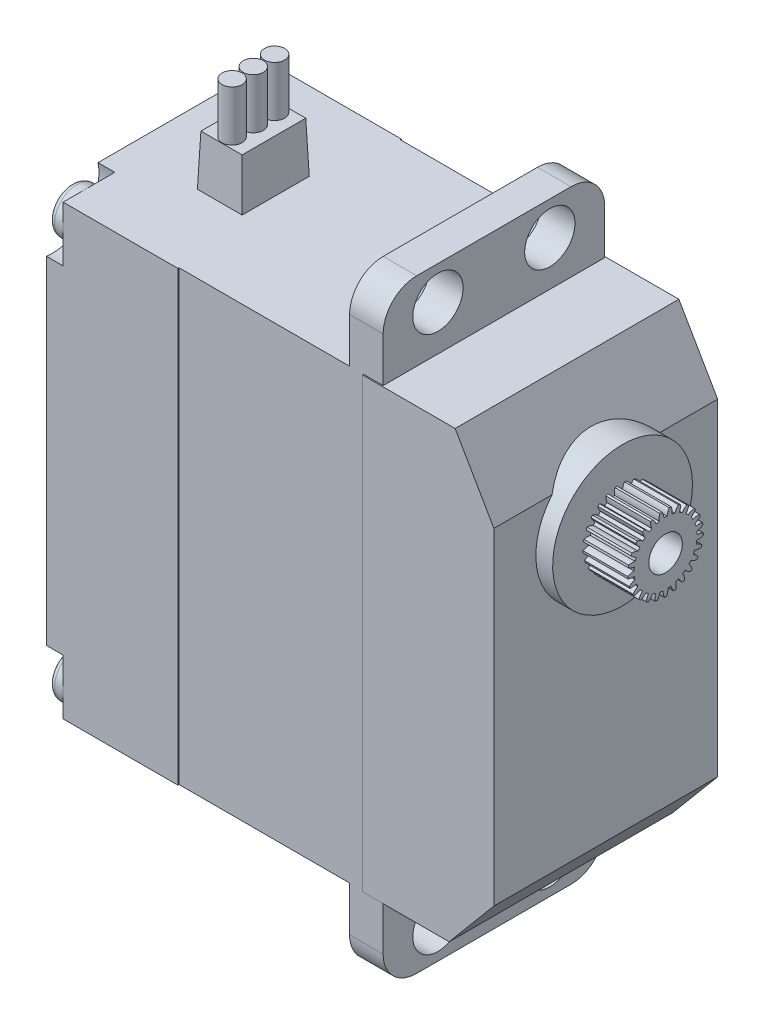
SolidWorks part; units mm, degrees
ref_plane "前视基准面" through (0, 0, 0) normal (0, 0, 1) x (1, 0, 0)
ref_plane "上视基准面" through (0, 0, 0) normal (0, 1, 0) x (1, 0, 0)
ref_plane "右视基准面" through (0, 0, 0) normal (1, 0, 0) x (0, 0, -1)
sketch "草图1" plane through (0, 0, 0) normal (0, 0, 1) x (1, 0, 0)
  line L1 (-20, -20) -> (20, -20)
  line L2 (-20, -20) -> (-20, 20)
  line L3 (-20, 20) -> (20, 20)
  line L4 (20, -20) -> (20, 20)
  line L5 (-20, -20) -> (20, 20) construction
  line L6 (-20, 20) -> (20, -20) construction
  point P0 (0, 0)
  dimension "D1" = 40
  dimension "D2" = 40
extrude "凸台-拉伸1" add sketch "草图1" along normal blind 20
ref_plane "基准面1" through (20, 0, 0) normal (1, 0, 0) x (0, 0, -1)
sketch "草图2" plane through (20, 0, 0) normal (1, 0, 0) x (0, 0, -1)
  line L0 (-10, 20) -> (-10, 10) construction
  line L1 (-20, 20) -> (0, 20) construction
  circle A0 centre (-10, 10) radius 6.25
  dimension "D2" = 12.5
  dimension "D1" = 10
extrude "凸台-拉伸2" add sketch "草图2" along normal blind 1.5
ref_plane "基准面2" through (-20, 0, 0) normal (-1, 0, 0) x (0, 0, 1)
ref_plane "基准面5" through (20, 0, 0) normal (1, 0, 0) x (0, 0, -1)
ref_plane "基准面8" through (0, 0, 0) normal (0, 0, -1) x (-1, 0, 0)
sketch "草图10" plane through (0, 0, 0) normal (0, 0, -1) x (-1, 0, 0)
  line L0 (-20, 20) -> (20, 20) construction
  line L1 (-8.25, -20) -> (8.25, -20)
  line L2 (-8.25, -20) -> (-8.25, 20)
  line L3 (-8.25, 20) -> (8.25, 20)
  line L4 (8.25, -20) -> (8.25, 20)
  line L5 (-8.25, -20) -> (8.25, 20) construction
  line L6 (-8.25, 20) -> (8.25, -20) construction
  point P0 (0, 0)
  dimension "D1" = 16.5
extrude "切除-拉伸5" cut sketch "草图10" against normal blind 0.1
ref_plane "基准面9" through (0, 0, 20) normal (0, 0, 1) x (1, 0, 0)
sketch "草图11" plane through (0, 0, 20) normal (0, 0, 1) x (1, 0, 0)
  line L0 (20, 20) -> (-20, 20) construction
  line L1 (-8.25, -20) -> (8.25, -20)
  line L2 (-8.25, -20) -> (-8.25, 20)
  line L3 (-8.25, 20) -> (8.25, 20)
  line L4 (8.25, -20) -> (8.25, 20)
  line L5 (-8.25, -20) -> (8.25, 20) construction
  line L6 (-8.25, 20) -> (8.25, -20) construction
  point P0 (0, 0)
  dimension "D1" = 16.5
extrude "切除-拉伸6" cut sketch "草图11" against normal blind 0.1
ref_plane "基准面10" through (0, 20, 0) normal (0, 1, 0) x (1, 0, 0)
ref_plane "基准面11" through (0, -20, 0) normal (0, -1, 0) x (-1, 0, 0)
ref_plane "基准面12" through (21.5, 0, 0) normal (1, 0, 0) x (0, 0, -1)
sketch "草图14" plane through (21.5, 0, 0) normal (1, 0, 0) x (0, 0, -1)
  arc A0 (-9.0018, 13.0728) -> (-9.3214, 12.5861) centre (-8.1454, 12.1623) ccw
  arc A1 (-9.3214, 12.5861) -> (-9.5931, 12.6558) centre (-10.1556, 9.9012) ccw
  arc A2 (-9.5931, 12.6558) -> (-9.6387, 13.2363) centre (-10.8278, 12.851) ccw
  arc A3 (-9.6387, 13.2363) -> (-9.8268, 13.2601) centre (-10.1556, 9.9012) ccw
  arc A4 (-9.8268, 13.2601) -> (-10.0153, 12.7092) centre (-8.7709, 12.5912) ccw
  arc A5 (-10.0153, 12.7092) -> (-10.2958, 12.7092) centre (-10.1556, 9.9012) ccw
  arc A6 (-10.2958, 12.7092) -> (-10.4843, 13.2601) centre (-11.5402, 12.5912) ccw
  arc A7 (-10.4843, 13.2601) -> (-10.6725, 13.2363) centre (-10.1556, 9.9012) ccw
  arc A8 (-10.6725, 13.2363) -> (-10.718, 12.6558) centre (-9.4834, 12.851) ccw
  arc A9 (-10.718, 12.6558) -> (-10.9897, 12.5861) centre (-10.1556, 9.9012) ccw
  arc A10 (-10.9897, 12.5861) -> (-11.3093, 13.0728) centre (-12.1657, 12.1623) ccw
  arc A11 (-11.3093, 13.0728) -> (-11.4857, 13.003) centre (-10.1556, 9.9012) ccw
  arc A12 (-11.4857, 13.003) -> (-11.3854, 12.4294) centre (-10.2381, 12.9255) ccw
  arc A13 (-11.3854, 12.4294) -> (-11.6312, 12.2943) centre (-10.1556, 9.9012) ccw
  arc A14 (-11.6312, 12.2943) -> (-12.0618, 12.6863) centre (-12.6649, 11.5913) ccw
  arc A15 (-12.0618, 12.6863) -> (-12.2153, 12.5748) centre (-10.1556, 9.9012) ccw
  arc A16 (-12.2153, 12.5748) -> (-11.9755, 12.0441) centre (-10.9876, 12.81) ccw
  arc A17 (-11.9755, 12.0441) -> (-12.18, 11.8521) centre (-10.1556, 9.9012) ccw
  arc A18 (-12.18, 11.8521) -> (-12.6946, 12.1247) centre (-13.0064, 10.9142) ccw
  arc A19 (-12.6946, 12.1247) -> (-12.8155, 11.9785) centre (-10.1556, 9.9012) ccw
  arc A20 (-12.8155, 11.9785) -> (-12.4513, 11.5242) centre (-11.6848, 12.5117) ccw
  arc A21 (-12.4513, 11.5242) -> (-12.6016, 11.2873) centre (-10.1556, 9.9012) ccw
  arc A22 (-12.6016, 11.2873) -> (-13.1678, 11.4234) centre (-13.1688, 10.1734) ccw
  arc A23 (-13.1678, 11.4234) -> (-13.2485, 11.2518) centre (-10.1556, 9.9012) ccw
  arc A24 (-13.2485, 11.2518) -> (-12.7828, 10.9023) centre (-12.286, 12.0493) ccw
  arc A25 (-12.7828, 10.9023) -> (-12.8695, 10.6355) centre (-10.1556, 9.9012) ccw
  arc A26 (-12.8695, 10.6355) -> (-13.4517, 10.6265) centre (-13.1418, 9.4155) ccw
  arc A27 (-13.4517, 10.6265) -> (-13.4872, 10.4402) centre (-10.1556, 9.9012) ccw
  arc A28 (-13.4872, 10.4402) -> (-12.9492, 10.2175) centre (-12.7533, 11.452) ccw
  arc A29 (-12.9492, 10.2175) -> (-12.9668, 9.9375) centre (-10.1556, 9.9012) ccw
  arc A30 (-12.9668, 9.9375) -> (-13.5285, 9.784) centre (-12.9272, 8.6881) ccw
  arc A31 (-13.5285, 9.784) -> (-13.5166, 9.5947) centre (-10.1556, 9.9012) ccw
  arc A32 (-13.5166, 9.5947) -> (-12.9401, 9.5128) centre (-13.0574, 10.7573) ccw
  arc A33 (-12.9401, 9.5128) -> (-12.8875, 9.2372) centre (-10.1556, 9.9012) ccw
  arc A34 (-12.8875, 9.2372) -> (-13.3934, 8.9488) centre (-12.5384, 8.0369) ccw
  arc A35 (-13.3934, 8.9488) -> (-13.3348, 8.7685) centre (-10.1556, 9.9012) ccw
  arc A36 (-13.3348, 8.7685) -> (-12.756, 8.8325) centre (-13.1791, 10.0087) ccw
  arc A37 (-12.756, 8.8325) -> (-12.6366, 8.5787) centre (-10.1556, 9.9012) ccw
  arc A38 (-12.6366, 8.5787) -> (-13.0549, 8.1735) centre (-12, 7.5029) ccw
  arc A39 (-13.0549, 8.1735) -> (-12.9532, 8.0134) centre (-10.1556, 9.9012) ccw
  arc A40 (-12.9532, 8.0134) -> (-12.4086, 8.2194) centre (-13.1109, 9.2534) ccw
  arc A41 (-12.4086, 8.2194) -> (-12.2298, 8.0032) centre (-10.1556, 9.9012) ccw
  arc A42 (-12.2298, 8.0032) -> (-12.5341, 7.5068) centre (-11.3456, 7.1196) ccw
  arc A43 (-12.5341, 7.5068) -> (-12.3959, 7.3769) centre (-10.1556, 9.9012) ccw
  arc A44 (-12.3959, 7.3769) -> (-11.9195, 7.7119) centre (-12.8569, 8.5388) ccw
  arc A45 (-11.9195, 7.7119) -> (-11.6926, 7.547) centre (-10.1556, 9.9012) ccw
  arc A46 (-11.6926, 7.547) -> (-11.8639, 6.9905) centre (-10.6165, 6.911) ccw
  arc A47 (-11.8639, 6.9905) -> (-11.6977, 6.8991) centre (-10.1556, 9.9012) ccw
  arc A48 (-11.6977, 6.8991) -> (-11.3197, 7.342) centre (-12.4333, 7.9098) ccw
  arc A49 (-11.3197, 7.342) -> (-11.0588, 7.2387) centre (-10.1556, 9.9012) ccw
  arc A50 (-11.0588, 7.2387) -> (-11.0864, 6.6571) centre (-9.8584, 6.8903) ccw
  arc A51 (-11.0864, 6.6571) -> (-10.9027, 6.6099) centre (-10.1556, 9.9012) ccw
  arc A52 (-10.9027, 6.6099) -> (-10.6467, 7.1329) centre (-11.8665, 7.4059) ccw
  arc A53 (-10.6467, 7.1329) -> (-10.3683, 7.0977) centre (-10.1556, 9.9012) ccw
  arc A54 (-10.3683, 7.0977) -> (-10.2504, 6.5275) centre (-9.1189, 7.0588) ccw
  arc A55 (-10.2504, 6.5275) -> (-10.0607, 6.5275) centre (-10.1556, 9.9012) ccw
  arc A56 (-10.0607, 6.5275) -> (-9.9428, 7.0977) centre (-11.1922, 7.0588) ccw
  arc A57 (-9.9428, 7.0977) -> (-9.6645, 7.1329) centre (-10.1556, 9.9012) ccw
  arc A58 (-9.6645, 7.1329) -> (-9.4084, 6.6099) centre (-8.4447, 7.4059) ccw
  arc A59 (-9.4084, 6.6099) -> (-9.2247, 6.6571) centre (-10.1556, 9.9012) ccw
  arc A60 (-9.2247, 6.6571) -> (-9.2523, 7.2387) centre (-10.4528, 6.8903) ccw
  arc A61 (-9.2523, 7.2387) -> (-8.9915, 7.342) centre (-10.1556, 9.9012) ccw
  arc A62 (-8.9915, 7.342) -> (-8.6134, 6.8991) centre (-7.8779, 7.9098) ccw
  arc A63 (-8.6134, 6.8991) -> (-8.4472, 6.9905) centre (-10.1556, 9.9012) ccw
  arc A64 (-8.4472, 6.9905) -> (-8.6185, 7.547) centre (-9.6947, 6.911) ccw
  arc A65 (-8.6185, 7.547) -> (-8.3916, 7.7119) centre (-10.1556, 9.9012) ccw
  arc A66 (-8.3916, 7.7119) -> (-7.9153, 7.3769) centre (-7.4542, 8.5388) ccw
  arc A67 (-7.9153, 7.3769) -> (-7.777, 7.5068) centre (-10.1556, 9.9012) ccw
  arc A68 (-7.777, 7.5068) -> (-8.0814, 8.0032) centre (-8.9655, 7.1196) ccw
  arc A69 (-8.0814, 8.0032) -> (-7.9026, 8.2194) centre (-10.1556, 9.9012) ccw
  arc A70 (-7.9026, 8.2194) -> (-7.3579, 8.0134) centre (-7.2003, 9.2534) ccw
  arc A71 (-7.3579, 8.0134) -> (-7.2563, 8.1735) centre (-10.1556, 9.9012) ccw
  arc A72 (-7.2563, 8.1735) -> (-7.6745, 8.5787) centre (-8.3112, 7.5029) ccw
  arc A73 (-7.6745, 8.5787) -> (-7.5551, 8.8325) centre (-10.1556, 9.9012) ccw
  arc A74 (-7.5551, 8.8325) -> (-6.9763, 8.7685) centre (-7.132, 10.0087) ccw
  arc A75 (-6.9763, 8.7685) -> (-6.9177, 8.9488) centre (-10.1556, 9.9012) ccw
  arc A76 (-6.9177, 8.9488) -> (-7.4236, 9.2372) centre (-7.7727, 8.0369) ccw
  arc A77 (-7.4236, 9.2372) -> (-7.371, 9.5128) centre (-10.1556, 9.9012) ccw
  arc A78 (-7.371, 9.5128) -> (-6.7945, 9.5947) centre (-7.2538, 10.7573) ccw
  arc A79 (-6.7945, 9.5947) -> (-6.7826, 9.784) centre (-10.1556, 9.9012) ccw
  arc A80 (-6.7826, 9.784) -> (-7.3443, 9.9375) centre (-7.3839, 8.6881) ccw
  arc A81 (-7.3443, 9.9375) -> (-7.3619, 10.2175) centre (-10.1556, 9.9012) ccw
  arc A82 (-7.3619, 10.2175) -> (-6.8239, 10.4402) centre (-7.5578, 11.452) ccw
  arc A83 (-6.8239, 10.4402) -> (-6.8594, 10.6265) centre (-10.1556, 9.9012) ccw
  arc A84 (-6.8594, 10.6265) -> (-7.4417, 10.6355) centre (-7.1693, 9.4155) ccw
  arc A85 (-7.4417, 10.6355) -> (-7.5283, 10.9023) centre (-10.1556, 9.9012) ccw
  arc A86 (-7.5283, 10.9023) -> (-7.0626, 11.2518) centre (-8.0251, 12.0493) ccw
  arc A87 (-7.0626, 11.2518) -> (-7.1434, 11.4234) centre (-10.1556, 9.9012) ccw
  arc A88 (-7.1434, 11.4234) -> (-7.7095, 11.2873) centre (-7.1424, 10.1734) ccw
  arc A89 (-7.7095, 11.2873) -> (-7.8599, 11.5242) centre (-10.1556, 9.9012) ccw
  arc A90 (-7.8599, 11.5242) -> (-7.4957, 11.9785) centre (-8.6263, 12.5117) ccw
  arc A91 (-7.4957, 11.9785) -> (-7.6166, 12.1247) centre (-10.1556, 9.9012) ccw
  arc A92 (-7.6166, 12.1247) -> (-8.1311, 11.8521) centre (-7.3047, 10.9142) ccw
  arc A93 (-8.1311, 11.8521) -> (-8.3356, 12.0441) centre (-10.1556, 9.9012) ccw
  arc A94 (-8.3356, 12.0441) -> (-8.0959, 12.5748) centre (-9.3235, 12.81) ccw
  arc A95 (-8.0959, 12.5748) -> (-8.2493, 12.6863) centre (-10.1556, 9.9012) ccw
  arc A96 (-8.2493, 12.6863) -> (-8.6799, 12.2943) centre (-7.6462, 11.5913) ccw
  arc A97 (-8.6799, 12.2943) -> (-8.9257, 12.4294) centre (-10.1556, 9.9012) ccw
  arc A98 (-8.9257, 12.4294) -> (-8.8255, 13.003) centre (-10.0731, 12.9255) ccw
  arc A99 (-8.8255, 13.003) -> (-9.0018, 13.0728) centre (-10.1556, 9.9012) ccw
extrude "凸台-拉伸6" add sketch "草图14" along normal blind 4
ref_plane "基准面13" through (25.5, 0, 0) normal (1, 0, 0) x (0, 0, -1)
sketch "草图15" plane through (25.5, 0, 0) normal (1, 0, 0) x (0, 0, -1)
  circle A0 centre (-10.1556, 9.9012) radius 1.5
extrude "切除-拉伸9" cut sketch "草图15" against normal blind 4
ref_plane "基准面14" through (0, 20, 0) normal (0, 1, 0) x (1, 0, 0)
ref_plane "基准面15" through (-20, 0, 0) normal (-1, 0, 0) x (0, 0, 1)
chamfer "倒角2" distance 6 angle 30 1 edges at (20, 20, 10) first distance on face at (20, 0, 10)
chamfer "倒角3" distance 4 angle 50 1 edges at (20, -20, 10) first distance on face at (0, -20, 10)
ref_plane "基准面18" through (0, -20, 0) normal (0, -1, 0) x (-1, 0, 0)
sketch "草图20" plane through (0, -20, 0) normal (0, -1, 0) x (-1, 0, 0)
  line L0 (-20, 1.0461) -> (-20, -15.8444) construction
  line L2 (-20, 0) -> (-7, 0) construction
  line L3 (6.4625, 0) -> (-6.4625, 0) construction
  line L4 (-7, 0) -> (-7, -0.8546) construction
  line L7 (-5.9416, -19.9) -> (-4.5261, -19.9) construction
  line L9 (-6.0182, -0.1) -> (-4.3371, -0.1) construction
  line L10 (-7, -0.1) -> (-7, -19.9) construction
  line L11 (-7, -19.9) -> (-10, -19.9) construction
  line L12 (-10, -19.9) -> (-10, 0) construction
  line L13 (-10, 0) -> (-7, 0) construction
  line L14 (-10, -0.1) -> (-7, -0.1)
  line L15 (-7, -0.1) -> (-7, -19.9)
  line L16 (-7, -19.9) -> (-10, -19.9)
  line L17 (-10, -19.9) -> (-10, -0.1)
extrude "凸台-拉伸8" add sketch "草图20" along normal blind 7
sketch "草图21" plane through (0, 20, 0) normal (0, 1, 0) x (1, 0, 0)
  line L6 (7, -19.9) -> (10, -19.9)
  line L7 (7, -0.1) -> (7, -19.9)
  line L8 (10, -0.1) -> (7, -0.1)
  line L9 (10, -19.9) -> (10, -0.1)
  line L10 (7, -19.9) -> (10, -19.9)
  line L11 (7, -0.1) -> (7, -19.9)
  line L12 (10, -0.1) -> (7, -0.1)
  line L13 (10, -19.9) -> (10, -0.1)
  dimension "D1" = 0
extrude "凸台-拉伸9" add sketch "草图21" along normal blind 7
fillet "圆角4" radius 3 4 edges at (8.5, 27, 19.9) (8.5, 27, 0.1) (8.5, -27, 19.9) (8.5, -27, 0.1)
ref_plane "基准面19" through (10, 0, 0) normal (1, 0, 0) x (0, 0, -1)
sketch "草图22" plane through (10, 0, 0) normal (1, 0, 0) x (0, 0, -1)
  line L3 (-20.5235, 0) -> (-0.5503, 0) construction
  circle A0 centre (-15, 24) radius 2.25
  circle A1 centre (-5, 24) radius 2.25
  circle A2 centre (-5, -24) radius 2.25
  circle A3 centre (-15, -24) radius 2.25
extrude "切除-拉伸12" cut sketch "草图22" against normal blind 7.3
sketch "草图24" plane through (-20, 0, 0) normal (-1, 0, 0) x (0, 0, 1)
  line L0 (20, 0) -> (0, 0) construction
  line L1 (20, -6.4625) -> (20, 6.4625) construction
  line L2 (10, 0) -> (10, 28.881) construction
  line L3 (0, 6.4625) -> (0, -6.4625) construction
  line L4 (11, 20) -> (-11, 20) construction
  line L5 (0, 15.0598) -> (0, 20)
  line L6 (0, 20) -> (4.6197, 20)
  line L7 (20, 15.0598) -> (20, 20)
  line L8 (20, 20) -> (15.3803, 20)
  line L9 (0, -20) -> (4.6197, -20)
  line L10 (0, -15.0598) -> (0, -20)
  line L11 (20, -20) -> (15.3803, -20)
  line L12 (20, -15.0598) -> (20, -20)
  arc A1 (4.6197, 20) -> (0, 15.0598) centre (0.55, 19.1756) cw
  arc A2 (15.3803, 20) -> (20, 15.0598) centre (19.45, 19.1756) ccw
  arc A3 (4.6197, -20) -> (0, -15.0598) centre (0.55, -19.1756) ccw
  arc A5 (15.3803, -20) -> (20, -15.0598) centre (19.45, -19.1756) cw
extrude "切除-拉伸13" cut sketch "草图24" against normal blind 1.5
ref_plane "基准面20" through (-18.5, 0, 0) normal (-1, 0, 0) x (0, 0, 1)
sketch "草图25" plane through (-18.5, 0, 0) normal (-1, 0, 0) x (0, 0, 1)
  line L0 (0, 0) -> (20, 0) construction
  line L1 (20, -6.4625) -> (20, 6.4625) construction
  line L2 (10, 0) -> (10, 8.1993) construction
  circle A0 centre (2.0399, 17.9472) radius 2
  circle A1 centre (17.9601, 17.9472) radius 2
  circle A2 centre (2.0399, -17.9472) radius 2
  circle A3 centre (17.9601, -17.9472) radius 2
extrude "凸台-拉伸10" add sketch "草图25" along normal blind 1.3
fillet "圆角5" radius 0.5 4 edges at (-19.8, -17.9472, 19.9601) (-19.8, -17.9472, 0.0399) (-19.8, 17.9472, 15.9601) (-19.8, 17.9472, 4.0399)
ref_plane "基准面21" through (-19.8, 0, 0) normal (-1, 0, 0) x (0, 0, 1)
sketch "草图26" plane through (-19.8, 0, 0) normal (-1, 0, 0) x (0, 0, 1)
  line L0 (1.6399, 18.3472) -> (0.5942, 18.3472)
  line L1 (1.6399, 16.5015) -> (2.4399, 16.5015)
  line L2 (1.6399, 16.5015) -> (1.6399, 17.5472)
  line L3 (1.6399, 19.3929) -> (2.4399, 19.3929)
  line L4 (2.4399, 16.5015) -> (2.4399, 17.5472)
  line L5 (1.6399, 16.5015) -> (2.4399, 19.3929) construction
  line L6 (1.6399, 19.3929) -> (2.4399, 16.5015) construction
  line L7 (3.4855, 17.5472) -> (2.4399, 17.5472)
  line L8 (3.4855, 17.5472) -> (3.4855, 18.3472)
  line L9 (3.4855, 18.3472) -> (2.4399, 18.3472)
  line L10 (0.5942, 17.5472) -> (0.5942, 18.3472)
  line L11 (3.4855, 17.5472) -> (0.5942, 18.3472) construction
  line L12 (3.4855, 18.3472) -> (0.5942, 17.5472) construction
  line L13 (2.4399, 18.3472) -> (2.4399, 19.3929)
  line L14 (1.6399, 17.5472) -> (0.5942, 17.5472)
  line L15 (1.6399, 18.3472) -> (1.6399, 19.3929)
  line L16 (0, 0) -> (20.0276, 0) construction
  line L17 (10.0138, 0) -> (10.0138, 3.4562) construction
  line L18 (16.542, 18.3472) -> (19.4334, 17.5472) construction
  line L19 (16.542, 17.5472) -> (19.4334, 18.3472) construction
  line L20 (18.3877, 19.3929) -> (17.5877, 16.5015) construction
  line L21 (18.3877, 16.5015) -> (17.5877, 19.3929) construction
  line L22 (18.3877, 18.3472) -> (18.3877, 19.3929)
  line L23 (18.3877, 17.5472) -> (19.4334, 17.5472)
  line L24 (17.5877, 18.3472) -> (17.5877, 19.3929)
  line L25 (19.4334, 17.5472) -> (19.4334, 18.3472)
  line L26 (16.542, 18.3472) -> (17.5877, 18.3472)
  line L27 (16.542, 17.5472) -> (16.542, 18.3472)
  line L28 (16.542, 17.5472) -> (17.5877, 17.5472)
  line L29 (17.5877, 16.5015) -> (17.5877, 17.5472)
  line L30 (18.3877, 19.3929) -> (17.5877, 19.3929)
  line L31 (18.3877, 16.5015) -> (18.3877, 17.5472)
  line L32 (18.3877, 16.5015) -> (17.5877, 16.5015)
  line L33 (18.3877, 18.3472) -> (19.4334, 18.3472)
  line L34 (18.3877, -16.5015) -> (17.5877, -19.3929) construction
  line L35 (18.3877, -19.3929) -> (17.5877, -16.5015) construction
  line L36 (16.542, -17.5472) -> (19.4334, -18.3472) construction
  line L37 (16.542, -18.3472) -> (19.4334, -17.5472) construction
  line L38 (3.4855, -18.3472) -> (0.5942, -17.5472) construction
  line L39 (3.4855, -17.5472) -> (0.5942, -18.3472) construction
  line L40 (1.6399, -19.3929) -> (2.4399, -16.5015) construction
  line L41 (1.6399, -16.5015) -> (2.4399, -19.3929) construction
  line L42 (18.3877, -18.3472) -> (19.4334, -18.3472)
  line L43 (18.3877, -16.5015) -> (17.5877, -16.5015)
  line L44 (18.3877, -16.5015) -> (18.3877, -17.5472)
  line L45 (18.3877, -19.3929) -> (17.5877, -19.3929)
  line L46 (17.5877, -16.5015) -> (17.5877, -17.5472)
  line L47 (16.542, -17.5472) -> (17.5877, -17.5472)
  line L48 (16.542, -17.5472) -> (16.542, -18.3472)
  line L49 (16.542, -18.3472) -> (17.5877, -18.3472)
  line L50 (19.4334, -17.5472) -> (19.4334, -18.3472)
  line L51 (17.5877, -18.3472) -> (17.5877, -19.3929)
  line L52 (18.3877, -17.5472) -> (19.4334, -17.5472)
  line L53 (18.3877, -18.3472) -> (18.3877, -19.3929)
  line L54 (1.6399, -18.3472) -> (1.6399, -19.3929)
  line L55 (1.6399, -17.5472) -> (0.5942, -17.5472)
  line L56 (2.4399, -18.3472) -> (2.4399, -19.3929)
  line L57 (0.5942, -17.5472) -> (0.5942, -18.3472)
  line L58 (3.4855, -18.3472) -> (2.4399, -18.3472)
  line L59 (3.4855, -17.5472) -> (3.4855, -18.3472)
  line L60 (3.4855, -17.5472) -> (2.4399, -17.5472)
  line L61 (2.4399, -16.5015) -> (2.4399, -17.5472)
  line L62 (1.6399, -19.3929) -> (2.4399, -19.3929)
  line L63 (1.6399, -16.5015) -> (1.6399, -17.5472)
  line L64 (1.6399, -16.5015) -> (2.4399, -16.5015)
  line L65 (1.6399, -18.3472) -> (0.5942, -18.3472)
  circle A0 centre (2.0399, 17.9472) radius 1.5 construction
  point P0 (2.0399, 17.9472)
  point P8 (2.0399, 17.9472)
  point P34 (17.9877, 17.9472)
  point P59 (17.9877, -17.9472)
  point P60 (2.0399, -17.9472)
extrude "切除-拉伸14" cut sketch "草图26" against normal blind 0.8 draft 16
ref_plane "基准面22" through (0, 20, 0) normal (0, 1, 0) x (1, 0, 0)
sketch "草图28" plane through (0, 20, 0) normal (0, 1, 0) x (1, 0, 0)
  line L0 (-20, 0) -> (-20, -20) construction
  line L1 (-20, 11) -> (-20, -11) construction
  line L2 (-6.4625, -20) -> (6.4625, -20) construction
  line L3 (-20, -10) -> (-10.9126, -10) construction
  line L4 (-20, -10) -> (-9.5, -10) construction
  line L5 (-9.5, -10) -> (-9.5, -7)
  line L6 (-9.5, -7) -> (-13.5, -7)
  line L7 (-13.5, -7) -> (-13.5, -13)
  line L8 (-13.5, -13) -> (-9.5, -13)
  line L9 (-9.5, -13) -> (-9.5, -10)
extrude "凸台-拉伸11" add sketch "草图28" along normal blind 4.5 draft 2
ref_plane "基准面23" through (0, 24.5, 0) normal (0, 1, 0) x (1, 0, 0)
sketch "草图29" plane through (0, 24.5, 0) normal (0, 1, 0) x (1, 0, 0)
  line L0 (-11.5, -7.1571) -> (-11.5, -14.7571) construction
  line L1 (-9.6571, -7.1571) -> (-13.3429, -7.1571) construction
  line L2 (-11.5, -10.9571) -> (-11.5, -7.1571) construction
  line L3 (-11.5, -10.9571) -> (-11.5, -12.8429) construction
  line L4 (-13.3429, -12.8429) -> (-9.6571, -12.8429) construction
  circle A0 centre (-11.5, -11.9) radius 0.9
  circle A1 centre (-11.5, -8.1) radius 0.9
  circle A2 centre (-11.5, -10.0025) radius 0.9
extrude "凸台-拉伸12" add sketch "草图29" along normal blind 4.5
